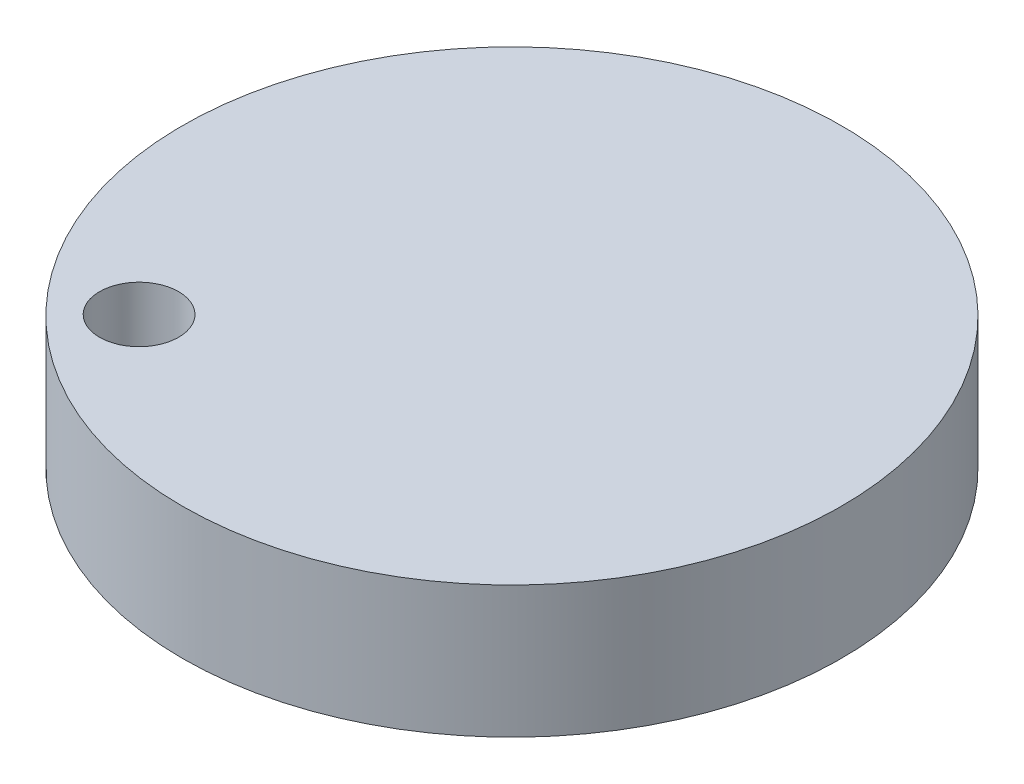
SolidWorks part; units mm, degrees
ref_plane "Front Plane" through (0, 0, 0) normal (0, 0, 1) x (1, 0, 0)
ref_plane "Top Plane" through (0, 0, 0) normal (0, 1, 0) x (1, 0, 0)
ref_plane "Right Plane" through (0, 0, 0) normal (1, 0, 0) x (0, 0, -1)
sketch "Sketch1" plane through (0, 0, 0) normal (0, 1, 0) x (1, 0, 0)
  circle A0 centre (0, 0) radius 12.5
  dimension "D1" = 25
extrude "Boss-Extrude1" add sketch "Sketch1" along normal blind 5
sketch "Sketch5" plane through (0, 0, 0) normal (0, -1, 0) x (1, 0, 0)
  line L0 (85.3333, 256) -> (426.6667, 256) construction
  line L1 (70.3333, 241) -> (411.6667, 241) construction
  line L20 (15.5994, -12.313) -> (15.5994, 14.2765) construction
  line L22 (-1.245, 0.1172) -> (0.0322, 3.1231)
  line L23 (1.5772, 0.1172) -> (0.0322, 3.1231)
  line L24 (0.0322, 3.1231) -> (1.5772, 0.1172)
  line L25 (-6.1218, -4.2841) -> (-6.614, -5.5378)
  line L26 (-3.2456, -2.8517) -> (-3.2003, -2.4439)
  line L27 (3.6668, 0.4484) -> (0.1519, 8.6268)
  line L28 (8.8353, -7.3566) -> (6.3322, -5.7535)
  line L29 (8.8353, -7.8036) -> (8.8353, -7.3566)
  line L30 (4.3982, -7.8036) -> (8.8353, -7.8036)
  line L31 (4.5863, -6.9096) -> (4.3982, -7.8036)
  line L32 (0.0322, 5.79) -> (2.5395, -1.2019)
  line L33 (-3.2003, -2.4439) -> (0.0322, 5.79)
  line L34 (-3.7831, -7.6989) -> (-3.6565, -6.5577)
  line L35 (-3.7831, -7.9389) -> (-3.7831, -7.6989)
  line L36 (-9.1214, -7.9389) -> (-3.7831, -7.9389)
  line L37 (-9.1214, -7.4584) -> (-9.1214, -7.9389)
  line L38 (-6.614, -5.5378) -> (-9.1214, -7.4584)
  line L39 (-0.9506, 8.8879) -> (-5.2069, -1.9539)
  arc A5 (1.5772, 0.1172) -> (-1.245, 0.1172) centre (0.1661, -0.1371) cw
  arc A6 (-0.9506, 8.8879) -> (-7.728, 2.3014) centre (-1.4867, 2.6593) cw
  arc A7 (0.1519, 9.24) -> (-7.728, 0.1172) centre (0.7835, 0.7298) cw
  arc A8 (0.1519, 9.24) -> (-7.728, 0.1172) centre (-0.8426, 2.1345) cw
  arc A9 (-0.9506, 8.8879) -> (-7.728, 2.3014) centre (-1.7737, 2.9547) cw
extrude "Boss-Extrude2" add sketch "Sketch5" along normal blind 2 contours A7 A8 | L34 A7 L25 L38 L37 L36 L35 | L28 A7 L31 L30 L29 | A9 A6 | A9 L26 L33 L32 L27 L39 | A5 L23 L22 region at (0.143, 0, 0.2845) region at (-6.1064, 0, -6.771) region at (-7.0063, 0, -2.1131) region at (6.5167, 0, -7.0826) region at (-4.2058, 0, -2.358) region at (-0.0825, 0, -2.9755)
sketch "Sketch7" plane through (0, 0, 0) normal (0, -1, 0) x (1, 0, 0)
  circle A0 centre (-7.1192, 7.0226) radius 1.5
  circle A1 centre (0, 0) radius 12.5 construction
  dimension "D2" = 3
  dimension "D1" = 10
extrude "Cut-Extrude1" cut sketch "Sketch7" against normal through all both and the other way through all
